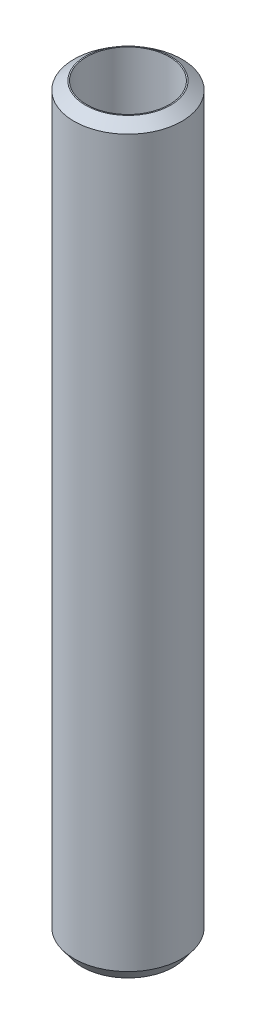
SolidWorks part; units mm, degrees
ref_plane "Front Plane" through (0, 0, 0) normal (0, 0, 1) x (1, 0, 0)
ref_plane "Top Plane" through (0, 0, 0) normal (0, 1, 0) x (1, 0, 0)
ref_plane "Right Plane" through (0, 0, 0) normal (1, 0, 0) x (0, 0, -1)
sketch "Sketch1" plane through (0, 0, 0) normal (0, 1, 0) x (1, 0, 0)
  circle A0 centre (0, 0) radius 22.5
  dimension "SHAFT_OD" = 45
extrude "Boss-Extrude1" add sketch "Sketch1" along normal blind 310.9324
sketch "Sketch2" plane through (0, 0, 0) normal (0, 1, 0) x (1, 0, 0)
  circle A0 centre (0, 0) radius 17.2753
  dimension "BORE_D" = 34.5506
extrude "Cut-Extrude1" cut sketch "Sketch2" along normal through all
chamfer "Chamfer1" distance 3.4299 angle 54.128 2 edges at (0, 310.9324, 22.5) (0, 0, 22.5) first distance on face at (0, 310.9324, 22.5) first distance on face at (0, 0, 17.2753)
